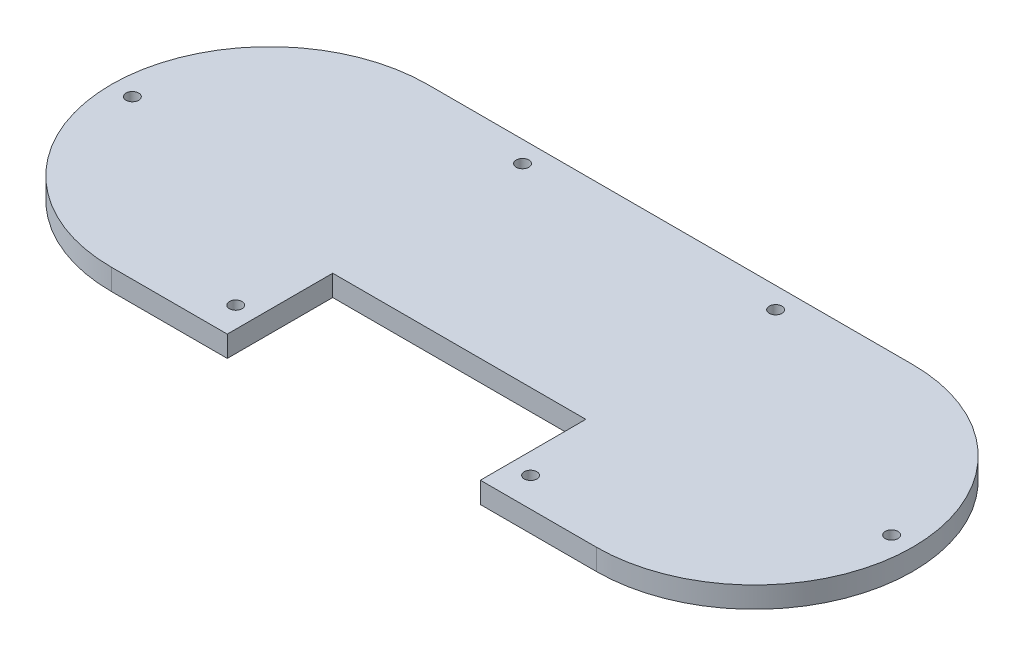
SolidWorks part; units mm, degrees
ref_plane "Front Plane" through (0, 0, 0) normal (0, 0, 1) x (1, 0, 0)
ref_plane "Top Plane" through (0, 0, 0) normal (0, 1, 0) x (1, 0, 0)
ref_plane "Right Plane" through (0, 0, 0) normal (1, 0, 0) x (0, 0, -1)
sketch "Sketch1" plane through (0, 0, 0) normal (0, 1, 0) x (1, 0, 0)
  line L0 (-57.5, 0) -> (57.5, 0) construction
  line L1 (-57.5, 37.5) -> (57.5, 37.5)
  line L2 (-57.5, -37.5) -> (-30, -37.5)
  line L3 (-57.5, 0) -> (-95, 0) construction
  line L4 (57.5, 0) -> (95, 0) construction
  line L5 (-30, -37.5) -> (-30, -12.5)
  line L6 (-30, -12.5) -> (30, -12.5)
  line L7 (30, -12.5) -> (30, -37.5)
  line L8 (0, 0) -> (0, -12.5) construction
  line L9 (30, -37.5) -> (57.5, -37.5)
  line L10 (-40, -35.5) -> (-30, -35.5) construction
  line L11 (-34.9497, -30.5503) -> (-34.9497, -37.5) construction
  line L12 (34.9497, -30.5503) -> (-34.9497, -30.5503) construction
  line L13 (-40, -35.5) -> (-40, -37.5) construction
  line L14 (-30, -35.5) -> (-34.9497, -30.5503) construction
  line L15 (30, -12.5) -> (30, 32.5) construction
  line L16 (30, 32.5) -> (30, 37.5) construction
  line L17 (30, 32.5) -> (-30, 32.5) construction
  line L18 (-30, 32.5) -> (-30, -12.5) construction
  line L19 (-34.9497, -30.5503) -> (-37.0711, -28.4289) construction
  line L20 (34.9497, -30.5503) -> (34.9497, -37.5) construction
  line L21 (0, -30.5503) -> (0, -12.5) construction
  arc A0 (-57.5, 37.5) -> (-57.5, -37.5) centre (-57.5, 0) ccw
  arc A1 (57.5, -37.5) -> (57.5, 37.5) centre (57.5, 0) ccw
  circle A2 centre (-90, 0) radius 1.5
  circle A3 centre (-30, 32.5) radius 1.5
  circle A4 centre (30, 32.5) radius 1.5
  circle A5 centre (90, 0) radius 1.5
  circle A6 centre (34.9497, -30.5503) radius 1.5
  circle A7 centre (-34.9497, -30.5503) radius 1.5
  arc A8 (-40, -35.5) -> (-30, -25.5) centre (-30, -35.5) cw construction
  point P3 (0, 0)
  dimension "D5" = 3
  dimension "D6" = 10
  dimension "D1" = 75
  dimension "D2" = 190
  dimension "D3" = 60
  dimension "D4" = 25
  dimension "D7" = 5
  dimension "D8" = 5
  dimension "D9" = 3
  dimension "D10" = 5
  dimension "D11" = 2
extrude "body" add sketch "Sketch1" along normal blind 5 contours L5 L6 L7 L9 A1 L1 A0 L2 | A7 | A2 | A3 | A4 | A5 | A6
